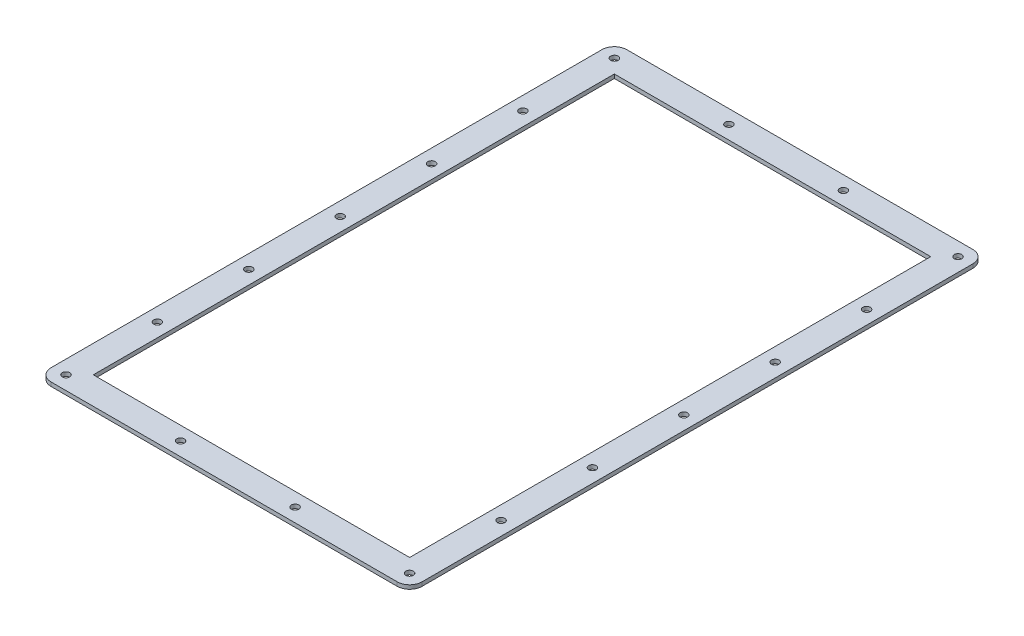
SolidWorks part; units mm, degrees
material "5052-H32"
ref_plane "Front Plane" through (0, 0, 0) normal (0, 0, 1) x (1, 0, 0)
ref_plane "Top Plane" through (0, 0, 0) normal (0, 1, 0) x (1, 0, 0)
ref_plane "Right Plane" through (0, 0, 0) normal (1, 0, 0) x (0, 0, -1)
sketch "Sketch1" plane through (0, 0, 0) normal (0, 1, 0) x (1, 0, 0)
  line L0 (-147, 192) -> (152, 192)
  line L1 (-125, -250) -> (130, -250)
  line L2 (-125, -250) -> (-125, 170)
  line L3 (-125, 170) -> (130, 170)
  line L4 (130, -250) -> (130, 170)
  line L5 (-125, -250) -> (130, 170) construction
  line L6 (-125, 170) -> (130, -250) construction
  line L7 (152, -272) -> (152, 192)
  line L8 (-147, -272) -> (152, -272)
  line L9 (-147, -272) -> (-147, 192)
  line L12 (130, -40) -> (-125, -40) construction
  circle A34 centre (141, 181) radius 3
  circle A35 centre (48.6667, 181) radius 3
  circle A36 centre (-43.6667, 181) radius 3
  circle A37 centre (-136, 181) radius 3
  circle A90 centre (141, 107.3333) radius 3
  circle A91 centre (141, 33.6667) radius 3
  circle A92 centre (141, -40) radius 3
  circle A93 centre (141, -113.6667) radius 3
  circle A94 centre (141, -187.3333) radius 3
  circle A102 centre (-136, 107.3333) radius 3
  circle A103 centre (141, -261) radius 3
  circle A106 centre (-136, 33.6667) radius 3
  circle A107 centre (48.6667, -261) radius 3
  circle A110 centre (-136, -40) radius 3
  circle A111 centre (-43.6667, -261) radius 3
  circle A114 centre (-136, -113.6667) radius 3
  circle A115 centre (-136, -261) radius 3
  circle A118 centre (-136, -187.3333) radius 3
  circle A119 centre (48.6667, -113.6667) radius 3 [skipped]
  circle A120 centre (-43.6667, -113.6667) radius 3 [skipped]
  circle A121 centre (48.6667, 107.3333) radius 3 [skipped]
  circle A122 centre (-43.6667, 107.3333) radius 3 [skipped]
  circle A123 centre (48.6667, 33.6667) radius 3 [skipped]
  circle A124 centre (48.6667, -40) radius 3 [skipped]
  circle A125 centre (-43.6667, -40) radius 3 [skipped]
  circle A126 centre (-43.6667, 33.6667) radius 3 [skipped]
  circle A127 centre (48.6667, -187.3333) radius 3 [skipped]
  circle A128 centre (-43.6667, -187.3333) radius 3 [skipped]
  dimension "D2" = 420
  dimension "D1" = 22
  dimension "D3" = 255
  dimension "D5" = 11
  dimension "D6" = 11
  dimension "D9" = 73.6667
  dimension "D10" = 92.3333
  dimension "D7" = 4
  dimension "D8" = 7
extrude "Boss-Extrude1" add sketch "Sketch1" along normal blind 3.175 contours L9 L8 L7 L0 L4 L1 L2 L3 A34 region at (2.5, 0, -186.4801)
fillet "Fillet1" radius 10 4 edges at (152, 1.5875, 272) (-147, 1.5875, 272) (152, 1.5875, -192) (-147, 1.5875, -192)
equation "\"L\"= 420mm"
equation "\"W\"= 255mm"
equation "\"H\"= 110mm"
equation "\"Compartment Width\"= 80"
equation "\"T\"= 4.7625 * 2 / 3mm"
equation "\"Inside Fillet Radius\"= 5.55625mm"
equation "\"Hole\"=25mm"
equation "\"D2@Sketch1\"=\"L\""
equation "\"D1@Boss-Extrude1\"=\"T\""
equation "\"D3@Sketch1\"=\"W\""
equation "\"D9@Sketch1\"=(\"L\"+22)/6"
equation "\"D10@Sketch1\"=(\"W\"+22)/3"
equation "\"Offset\"= 18mm"
equation "\"Wheel to Wall\"= 43"
